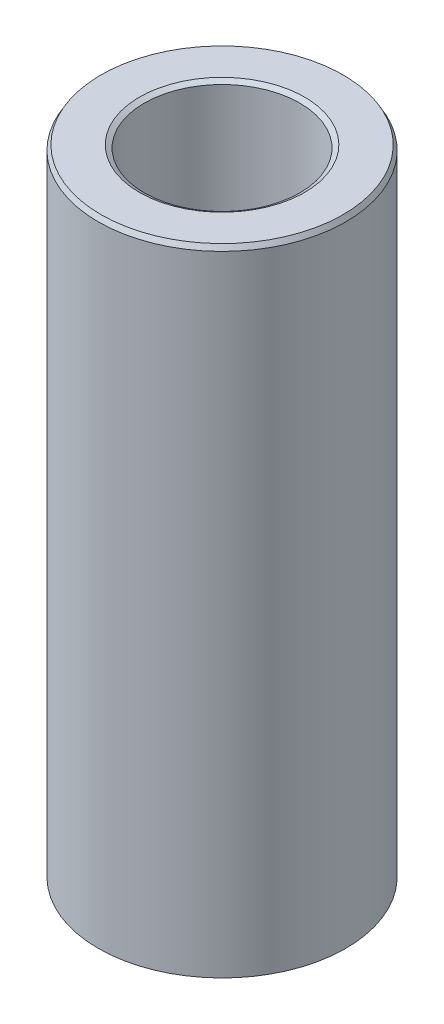
SolidWorks part; units mm, degrees
ref_plane "Front Plane" through (0, 0, 0) normal (0, 0, 1) x (1, 0, 0)
ref_plane "Top Plane" through (0, 0, 0) normal (0, 1, 0) x (1, 0, 0)
ref_plane "Right Plane" through (0, 0, 0) normal (1, 0, 0) x (0, 0, -1)
sketch "Sketch1" plane through (0, 0, 0) normal (0, 1, 0) x (1, 0, 0)
  circle A0 centre (0, 0) radius 60
  dimension "SLEEVE_OD" = 120
extrude "Boss-Extrude1" add sketch "Sketch1" along normal blind 308.5675
sketch "Sketch2" plane through (0, 0, 0) normal (0, 1, 0) x (1, 0, 0)
  circle A0 centre (0, 0) radius 37.6961
  dimension "BORE_D" = 75.3921
extrude "Cut-Extrude1" cut sketch "Sketch2" along normal through all
chamfer "Chamfer1" distance 2.336 angle 30 4 edges at (0, 308.5675, 37.6961) (0, 0, 37.6961) (0, 0, 60) (0, 308.5675, 60) first distance on face at (0, 308.5675, 37.6961) first distance on face at (0, 0, 37.6961) first distance on face at (0, 308.5675, 60)
